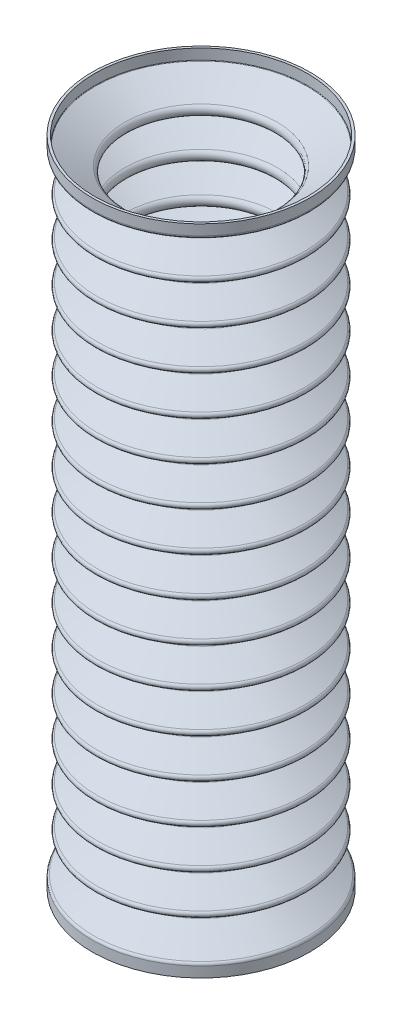
SolidWorks part; units mm, degrees
ref_plane "Front Plane" through (0, 0, 0) normal (0, 0, 1) x (1, 0, 0)
ref_plane "Top Plane" through (0, 0, 0) normal (0, 1, 0) x (1, 0, 0)
ref_plane "Right Plane" through (0, 0, 0) normal (1, 0, 0) x (0, 0, -1)
sketch "Sketch1" plane through (0, 0, 0) normal (0, 0, 1) x (1, 0, 0)
  line L0 (0, 0) -> (0, 317.5)
  line L1 (0, 0) -> (52.959, 0)
  line L2 (52.959, 0) -> (52.959, 5.0545)
  line L3 (35.052, 0) -> (35.052, 304.8) construction
  line L4 (52.1521, 6.3993) -> (37.5738, 14.1731)
  line L5 (37.5738, 16.8626) -> (50.4372, 23.7219)
  line L6 (35.052, 15.5178) -> (52.959, 15.5178) construction
  line L7 (52.959, 5.969) -> (52.959, 25.0666) construction
  line L8 (50.4372, 26.4114) -> (37.5738, 33.2707)
  line L9 (37.5738, 35.9602) -> (50.4372, 42.8195)
  line L10 (50.4372, 45.509) -> (37.5738, 52.3683)
  line L11 (37.5738, 55.0578) -> (50.4372, 61.9171)
  line L12 (50.4372, 64.6066) -> (37.5738, 71.4659)
  line L13 (37.5738, 74.1554) -> (50.4372, 81.0147)
  line L14 (50.4372, 83.7043) -> (37.5738, 90.5636)
  line L15 (37.5738, 93.2531) -> (50.4372, 100.1124)
  line L16 (50.4372, 102.8019) -> (37.5738, 109.6612)
  line L17 (37.5738, 112.3507) -> (50.4372, 119.21)
  line L18 (50.4372, 121.8995) -> (37.5738, 128.7588)
  line L19 (37.5738, 131.4483) -> (50.4372, 138.3076)
  line L20 (50.4372, 140.9971) -> (37.5738, 147.8564)
  line L21 (37.5738, 150.5459) -> (50.4372, 157.4052)
  line L22 (50.4372, 160.0948) -> (37.5738, 166.9541)
  line L23 (37.5738, 169.6436) -> (50.4372, 176.5029)
  line L24 (50.4372, 179.1924) -> (37.5738, 186.0517)
  line L25 (37.5738, 188.7412) -> (50.4372, 195.6005)
  line L26 (50.4372, 198.29) -> (37.5738, 205.1493)
  line L27 (37.5738, 207.8388) -> (50.4372, 214.6981)
  line L28 (50.4372, 217.3876) -> (37.5738, 224.2469)
  line L29 (37.5738, 226.9364) -> (50.4372, 233.7957)
  line L30 (50.4372, 236.4853) -> (37.5738, 243.3446)
  line L31 (37.5738, 246.0341) -> (50.4372, 252.8934)
  line L32 (50.4372, 255.5829) -> (37.5738, 262.4422)
  line L33 (37.5738, 265.1317) -> (50.4372, 271.991)
  line L34 (50.4372, 274.6805) -> (37.5738, 281.5398)
  line L35 (37.5738, 284.2293) -> (50.4372, 291.0886)
  line L36 (50.4372, 293.7781) -> (37.5738, 300.6374)
  line L37 (37.5738, 303.3269) -> (52.1521, 311.1007)
  line L38 (0, 158.75) -> (155.8281, 158.75) construction
  line L39 (52.959, 317.5) -> (52.959, 312.4455)
  line L40 (0, 317.5) -> (52.959, 317.5)
  arc A0 (52.959, 5.0545) -> (52.1521, 6.3993) centre (51.435, 5.0545) ccw
  arc A1 (52.959, 312.4455) -> (52.1521, 311.1007) centre (51.435, 312.4455) cw
  arc A2 (37.5738, 300.6374) -> (37.5738, 303.3269) centre (38.2909, 301.9822) cw
  arc A3 (50.4372, 291.0886) -> (50.4372, 293.7781) centre (49.7201, 292.4334) ccw
  arc A4 (37.5738, 281.5398) -> (37.5738, 284.2293) centre (38.2909, 282.8846) cw
  arc A5 (50.4372, 271.991) -> (50.4372, 274.6805) centre (49.7201, 273.3358) ccw
  arc A6 (37.5738, 262.4422) -> (37.5738, 265.1317) centre (38.2909, 263.7869) cw
  arc A7 (50.4372, 252.8934) -> (50.4372, 255.5829) centre (49.7201, 254.2381) ccw
  arc A8 (37.5738, 243.3446) -> (37.5738, 246.0341) centre (38.2909, 244.6893) cw
  arc A9 (50.4372, 233.7957) -> (50.4372, 236.4853) centre (49.7201, 235.1405) ccw
  arc A10 (37.5738, 224.2469) -> (37.5738, 226.9364) centre (38.2909, 225.5917) cw
  arc A11 (50.4372, 214.6981) -> (50.4372, 217.3876) centre (49.7201, 216.0429) ccw
  arc A12 (37.5738, 205.1493) -> (37.5738, 207.8388) centre (38.2909, 206.4941) cw
  arc A13 (50.4372, 195.6005) -> (50.4372, 198.29) centre (49.7201, 196.9453) ccw
  arc A14 (37.5738, 186.0517) -> (37.5738, 188.7412) centre (38.2909, 187.3964) cw
  arc A15 (50.4372, 176.5029) -> (50.4372, 179.1924) centre (49.7201, 177.8476) ccw
  arc A16 (37.5738, 166.9541) -> (37.5738, 169.6436) centre (38.2909, 168.2988) cw
  arc A17 (50.4372, 157.4052) -> (50.4372, 160.0948) centre (49.7201, 158.75) ccw
  arc A18 (37.5738, 147.8564) -> (37.5738, 150.5459) centre (38.2909, 149.2012) cw
  arc A19 (50.4372, 138.3076) -> (50.4372, 140.9971) centre (49.7201, 139.6524) ccw
  arc A20 (37.5738, 128.7588) -> (37.5738, 131.4483) centre (38.2909, 130.1036) cw
  arc A21 (50.4372, 119.21) -> (50.4372, 121.8995) centre (49.7201, 120.5548) ccw
  arc A22 (37.5738, 109.6612) -> (37.5738, 112.3507) centre (38.2909, 111.0059) cw
  arc A23 (50.4372, 100.1124) -> (50.4372, 102.8019) centre (49.7201, 101.4571) ccw
  arc A24 (37.5738, 90.5636) -> (37.5738, 93.2531) centre (38.2909, 91.9083) cw
  arc A25 (50.4372, 81.0147) -> (50.4372, 83.7043) centre (49.7201, 82.3595) ccw
  arc A26 (37.5738, 71.4659) -> (37.5738, 74.1554) centre (38.2909, 72.8107) cw
  arc A27 (50.4372, 61.9171) -> (50.4372, 64.6066) centre (49.7201, 63.2619) ccw
  arc A28 (37.5738, 52.3683) -> (37.5738, 55.0578) centre (38.2909, 53.7131) cw
  arc A29 (50.4372, 42.8195) -> (50.4372, 45.509) centre (49.7201, 44.1643) ccw
  arc A30 (37.5738, 33.2707) -> (37.5738, 35.9602) centre (38.2909, 34.6154) cw
  arc A31 (50.4372, 23.7219) -> (50.4372, 26.4114) centre (49.7201, 25.0666) ccw
  arc A32 (37.5738, 14.1731) -> (37.5738, 16.8626) centre (38.2909, 15.5178) cw
  point P12 (52.959, 15.5178)
  point P37 (52.959, 311.531)
  dimension "D7" = 1.524
  dimension "D1" = 52.959
  dimension "D2" = 5.969
  dimension "D3" = 317.5
  dimension "D4" = 35.052
  dimension "D6" = 19.0976
  dimension "D5" = 16
revolve "Revolve2" add sketch "Sketch1" angle 360 about L0
shell "Shell1" thickness 1.1938 removed face at (52.959, 0, 0) removed face at (52.959, 317.5, 0)
ref_axis "Axis1" through (0, 316.992, 0) along (0, -1, 0)
